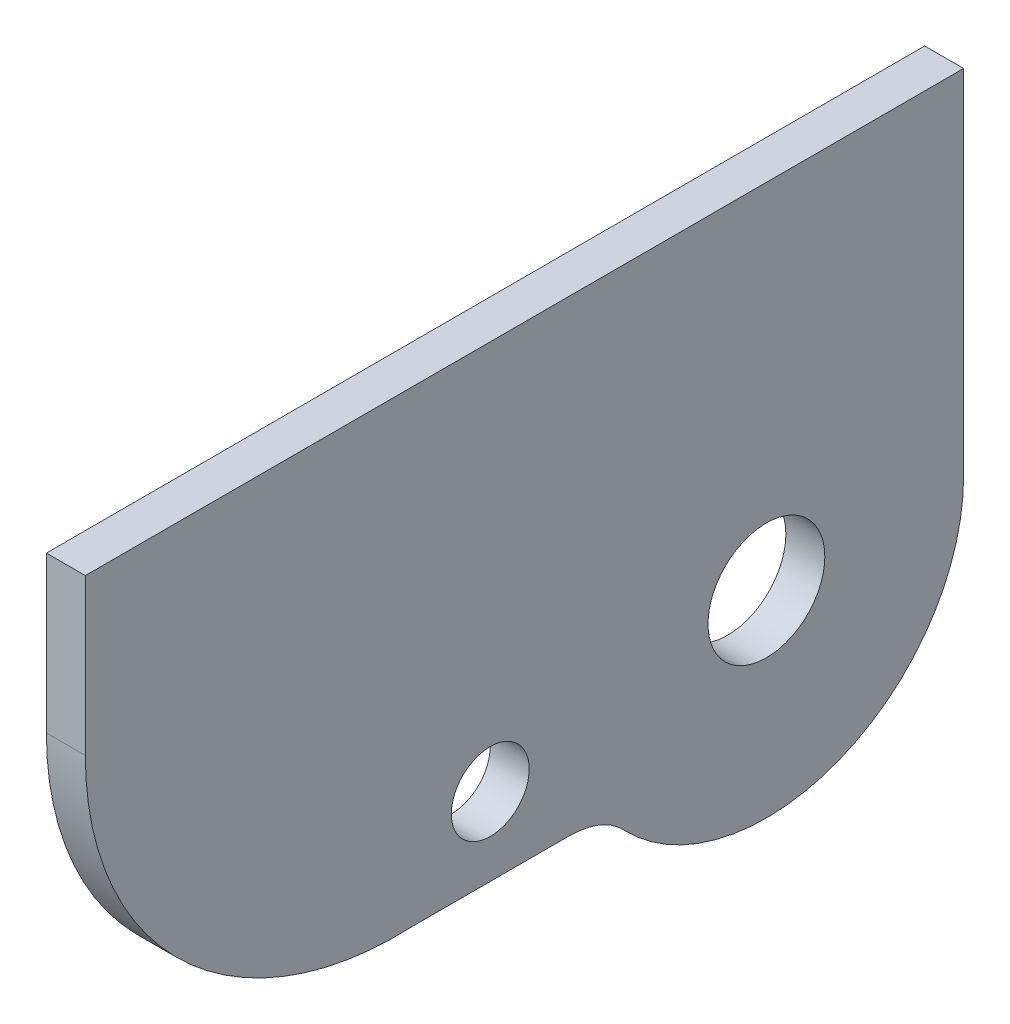
SolidWorks part; units mm, degrees
ref_plane "Front Plane" through (0, 0, 0) normal (0, 0, 1) x (1, 0, 0)
ref_plane "Top Plane" through (0, 0, 0) normal (0, 1, 0) x (1, 0, 0)
ref_plane "Right Plane" through (0, 0, 0) normal (1, 0, 0) x (0, 0, -1)
sketch "Sketch1" plane through (0, 0, 0) normal (1, 0, 0) x (0, 0, -1)
  line L0 (-53.2162, 59.5847) -> (89.9756, 59.5847)
  line L1 (89.9756, 59.5847) -> (89.9756, 1.9775)
  line L2 (-53.2162, 59.5847) -> (-53.2162, 34.1847)
  line L3 (153.2407, -143.7764) -> (143.5856, -133.7244) construction
  line L4 (0.0988, -16.6153) -> (25.4988, -16.6153)
  line L5 (166.6094, -16.6153) -> (149.3685, -16.6153) construction
  arc A0 (89.9756, 1.9775) -> (34.6347, -20.2955) centre (57.8231, 1.9775) cw
  arc A1 (-53.2162, 34.1847) -> (0.0988, -16.6153) centre (-2.3568, 34.1847) ccw
  circle A2 centre (12.7988, -3.9153) radius 6.35
  circle A6 centre (57.8231, 1.9775) radius 9.525
  spline S0 degree 3 poles (25.4988, -16.6153) (29.5448, -16.6153) (32.4898, -18.0624) (34.6347, -20.2955) knots 0 0 0 0 1 1 1 1
  point P11 (12.7988, -16.6153)
  dimension "D6" = 12.7
  dimension "D1" = 25.4
  dimension "D2" = 25.4
  dimension "D3" = 76.2
  dimension "D5" = 12.7
extrude "Boss-Extrude1" add sketch "Sketch1" along normal blind 6.35
